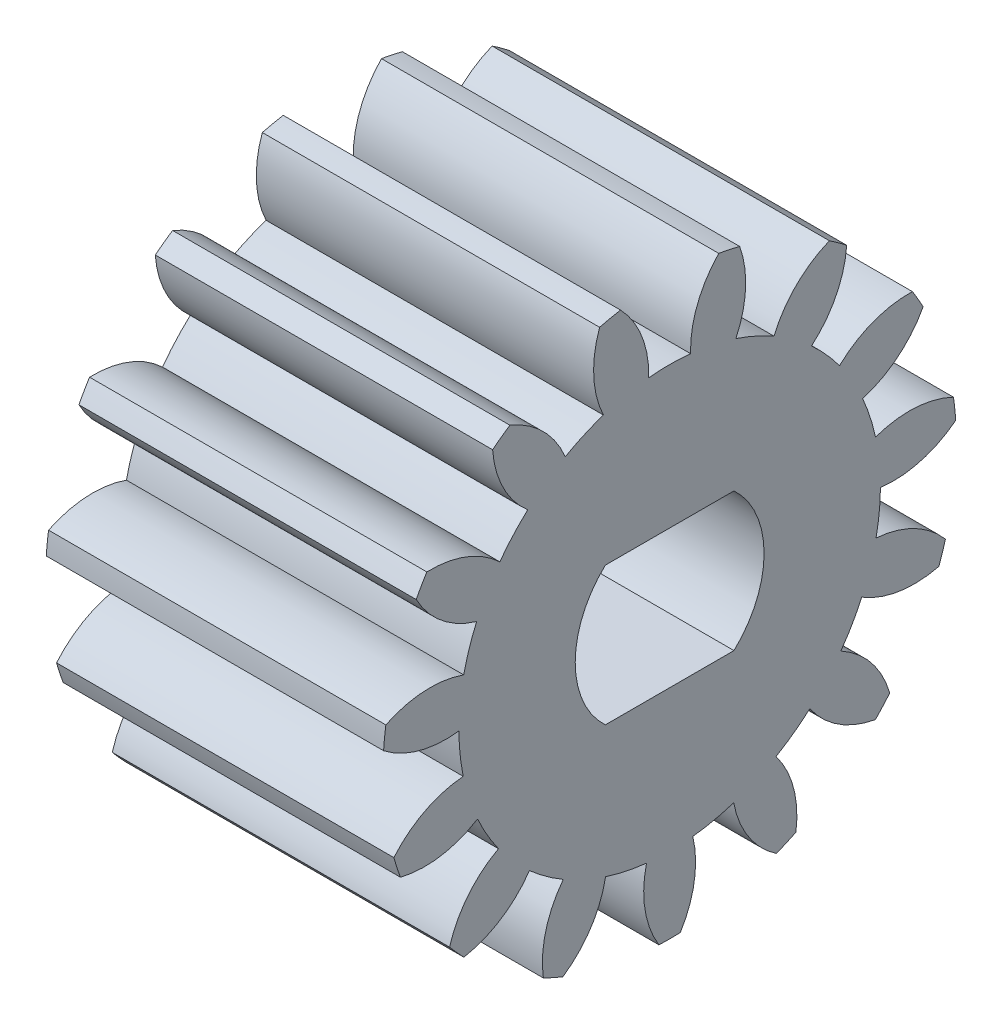
SolidWorks part; units mm, degrees
ref_plane "Plane1" through (0, 0, 0) normal (0, 0, 1) x (1, 0, 0)
ref_plane "Plane2" through (0, 0, 0) normal (0, 1, 0) x (1, 0, 0)
ref_plane "Plane3" through (0, 0, 0) normal (1, 0, 0) x (0, 0, -1)
sketch "HoldingSke" plane through (0, 0, 0) normal (0, 1, 0) x (1, 0, 0)
  line L0 (0, 0) -> (0.9659, -0.2588)
  line L1 (-15, 0) -> (100, 0) construction
  line L2 (0, 0) -> (-2.1039, 2.3779)
  line L3 (0, 0) -> (-11.863, 4.5341)
  line L4 (0, 0) -> (8.3417, 2.2352)
  line L5 (0, 0) -> (-46.8476, -17.4728)
  line L6 (0, 0) -> (-8.2896, -5.593)
  line L7 (-2.1039, 2.3779) -> (8.6586, 51.2059)
  line L8 (-76.2, 54.61) -> (-75.3, 54.61)
  line L9 (-67.7845, 28.3722) -> (-49.3413, 33.142)
  line L10 (-76.2, 71.12) -> (104.1128, 71.12)
  line L11 (0, 0) -> (-10, 0)
  line L12 (-76.2, 101.6) -> (-76.162, 101.6)
  line L13 (24.9733, 27.94) -> (52.9518, 28.4284)
  line L14 (24.9733, 27.94) -> (24.9743, 27.94)
  line L15 (24.9733, 27.94) -> (100.4006, 29.5858)
  line L16 (-63.627, -1) -> (-12.827, -1)
  circle A0 centre (0, 0) radius 2.5
  circle A1 centre (0, 0) radius 6.249
  circle A2 centre (0, 0) radius 37.5
  circle A3 centre (0, 0) radius 2.5
  dimension "MHD" = 12.498
  dimension "Hub_dia" = 75
  dimension "Bore" = 5
  dimension "MBD" = 5
  dimension "Num_teeth" = 15
  dimension "Pitch" = 1
  dimension "Overall_len" = 50
  dimension "Show_teeth" = 15
  dimension "Thickness" = 10
  dimension "OAL" = 50.0001
  dimension "T_dim" = 0.9
  dimension "Ap" = 14.5
  dimension "H" = 19.05
  dimension "Pitch_radius" = 180.3128
  dimension "Width" = 10
  dimension "Backlash" = 0.038
  dimension "Addendum_fac" = 1
  dimension "Dedendum_fac" = 1.25
  dimension "Clearance_fac" = 0.25
  dimension "Dedendum_add" = 0.001
  dimension "Module" = 1
sketch "BasProSke" plane through (0, 0, 0) normal (0, 1, 0) x (1, 0, 0)
  line L0 (-10, 0) -> (60, 0) construction
  line L1 (0, 0) -> (0, 8.5)
  line L2 (0, 0) -> (10, 0)
  line L3 (10, 0) -> (10, 8.5)
  line L4 (10, 8.5) -> (0, 8.5)
  dimension "Thickness" = 10
  dimension "Diameter" = 17
revolve "Base-Revolve" add sketch "BasProSke" angle 360 about L0
sketch "TooCutSke" plane through (0, 0, 0) normal (1, 0, 0) x (0, 0, -1)
  line L1 (0, 0) -> (0, 107) construction
  line L2 (0, 0) -> (-0.8504, 7.4516) construction
  line L3 (0, 0) -> (-3.1044, 14.6049) construction
  line L4 (-0.8504, 7.4516) -> (-1.5522, 7.3025) construction
  arc A0 (0.6195, 6.2182) -> (-0.6195, 6.2182) centre (0, 0) ccw
  arc A1 (1.4773, 8.3964) -> (-1.4773, 8.3964) centre (0, 0) ccw
  circle A2 centre (0, 0) radius 7.5 construction
  circle A3 centre (0, 0) radius 7.2611 construction
  arc A4 (-0.6195, 6.2182) -> (-1.4773, 8.3964) centre (-3.6186, 6.2952) ccw
  arc A5 (1.4773, 8.3964) -> (0.6195, 6.2182) centre (3.6186, 6.2952) ccw
  dimension "Root_dia" = 12.498
  dimension "Overcut_dia" = 17.0508
  dimension "Pitch_dia" = 15
  dimension "Base_dia" = 14.5222
  dimension "Flank_rad" = 3
  dimension "Half_ang" = 12
  dimension "Half_CT" = 0.7175
extrude "ToothCut" cut sketch "TooCutSke" along normal through all
fillet "Breaks" [suppressed] radius 0.02 tangent propagation no
fillet "RootFillets" [suppressed] radius 0.251
pattern_circular "TeethCuts" count 15 every 24 about axis through (-10, 0, 0) along (1, 0, 0) of "ToothCut", "RootFillets", "Breaks"
sketch "HubNeaOneSke" plane through (0, 0, 0) normal (-1, 0, 0) x (0, 0, 1)
  circle A0 centre (0, 0) radius 6.249
  dimension "Diameter" = 12.498
extrude "HubNearOne" [suppressed] add sketch "HubNeaOneSke" along normal blind 40.0001
sketch "HubNeaBotSke" plane through (0, 0, 0) normal (-1, 0, 0) x (0, 0, 1)
  circle A0 centre (0, 0) radius 6.249
  dimension "Diameter" = 12.498
extrude "HubNearBoth" [suppressed] add sketch "HubNeaBotSke" along normal blind 20
ref_plane "FarPln" through (10, 0, 0) normal (1, 0, 0) x (0, 0, -1)
sketch "HubFarSke" plane through (10, 0, 0) normal (1, 0, 0) x (0, 0, -1)
  circle A0 centre (0, 0) radius 6.249
  dimension "Diameter" = 12.498
extrude "HubFar" [suppressed] add sketch "HubFarSke" along normal blind 20
sketch "BorSke" plane through (0, 0, 0) normal (1, 0, 0) x (0, 0, -1)
  circle A0 centre (0, 0) radius 2.5
  dimension "Diameter" = 5
extrude "Bore" cut sketch "BorSke" along normal mid plane 100.0001
sketch "KeySke" plane through (0, 0, 0) normal (1, 0, 0) x (0, 0, -1)
  line L0 (-1, 0) -> (-1, 3.4)
  line L1 (-1, 3.4) -> (1, 3.4)
  line L2 (1, 3.4) -> (1, 0)
  line L3 (0, 0) -> (0, 34) construction
  line L4 (-1, 0) -> (1, 0)
  dimension "Offset" = 3.4
  dimension "Width" = 2
extrude "Keyway" [suppressed] cut sketch "KeySke" along normal mid plane 100.0001
pattern_circular "Keyway2" [suppressed] count 2 every 90 about axis through (-10, 0, 0) along (1, 0, 0) reverse direction yes
sketch "Sketch1" plane through (10, 0, 0) normal (1, 0, 0) x (0, 0, -1)
  line L0 (-1.9072, 2.05) -> (1.9072, 2.05)
  line L1 (-1.9072, -2.05) -> (1.9072, -2.05)
  circle A0 centre (0, 0) radius 2.8
  dimension "D1" = 5.6
  dimension "D2" = 4.1
  dimension "D3" = 2.05
extrude "Boss-Extrude1" add sketch "Sketch1" against normal through all contours L0 A0 | L1 A0 region at (10, 2.3537, 0) region at (10, -2.3537, 0)
extrude "Cut-Extrude1" cut sketch "Sketch1<3>" against normal blind 10 contours L0 A0 L1 region at (10, 0, 0)
sketch "Sketch1<3>" plane through (10, 0, 0) normal (1, 0, 0) x (0, 0, -1) same geometry as "Sketch1"
equation "' \"Module@HoldingSke\" = 6.35"
equation "' \"Num_teeth@HoldingSke\" = 12"
equation "' \"Ap@HoldingSke\" =  20"
equation "' \"Ap@HoldingSke\" = 20"
equation "' \"Width@HoldingSke\" = 0.5 * 25.4"
equation "' \"Hub_dia@HoldingSke\"= 1 * 25.4"
equation "' \"Hub_dia@HoldingSke\" = 1 * 25.4"
equation "' \"Overall_len@HoldingSke\" = 1.0 * 25.4"
equation "' \"Bore@HoldingSke\" = 0.75 * 25.4"
equation "' \"T_dim@HoldingSke\" = 0.1 * 25.4"
equation "' \"Width@KeySke\" = 0.25 * 25.4"
equation "' \"Show_teeth@HoldingSke\" = 13"
equation "' \"Backlash@HoldingSke\" = 0.009 * 25.4"
equation "' \"Addendum_fac@HoldingSke\" = 1.0"
equation "' \"Dedendum_fac@HoldingSke\" = 1.25"
equation "' \"Dedendum_add@HoldingSke\" = 0.00005 * 25.4"
equation "' \"Clearance_fac@HoldingSke\" = 0.25"
equation "\"Pitch@HoldingSke\" = 1 / \"Module@HoldingSke\""
equation "\"Overcut_dia@TooCutSke\" = (\"Num_teeth@HoldingSke\" + 2 * \"Addendum_fac@HoldingSke\") / \"Pitch@HoldingSke\" + 0.002 * 25.4"
equation "\"Pitch_dia@TooCutSke\" = \"Num_teeth@HoldingSke\" / \"Pitch@HoldingSke\""
equation "\"Base_dia@TooCutSke\" = \"Num_teeth@HoldingSke\" / \"Pitch@HoldingSke\" * cos((\"Ap@HoldingSke\"  * 3.14159265 / 180))"
equation "\"Root_dia@TooCutSke\" = (\"Num_teeth@HoldingSke\" + 2) / \"Pitch@HoldingSke\" - 2 * (\"Addendum_fac@HoldingSke\" + \"Dedendum_fac@HoldingSke\") / \"Pitch@HoldingSke\" - \"Dedendum_add@HoldingSke\" * 2"
equation "\"Half_ang@TooCutSke\" = 180 / \"Num_teeth@HoldingSke\""
equation "\"Half_CT@TooCutSke\" = \"Num_teeth@HoldingSke\" / \"Pitch@HoldingSke\" * sin((3.14159265 / 2 / \"Num_teeth@HoldingSke\")) / 2 - 7 * \"Backlash@HoldingSke\" / 4"
equation "\"Flank_rad@TooCutSke\" = \"Num_teeth@HoldingSke\" / \"Pitch@HoldingSke\" / 5"
equation "\"Radius@RootFillets\" = \"Clearance_fac@HoldingSke\" / \"Pitch@HoldingSke\" + \"Dedendum_add@HoldingSke\""
equation "\"Break_rad@Breaks\" = 0.02 / \"Pitch@HoldingSke\""
equation "\"Thickness@HoldingSke\" = \"Width@HoldingSke\""
equation "\"OAL@HoldingSke\" = \"Thickness@HoldingSke\""
equation "\"MHD@HoldingSke\" = (\"Num_teeth@HoldingSke\" + 2) / \"Pitch@HoldingSke\" - 2 * (\"Addendum_fac@HoldingSke\" + \"Dedendum_fac@HoldingSke\")  / \"Pitch@HoldingSke\" - \"Dedendum_add@HoldingSke\" * 2"
equation "\"MBD@HoldingSke\" = (\"Num_teeth@HoldingSke\" + 2) / \"Pitch@HoldingSke\" - 2 * (\"Addendum_fac@HoldingSke\" + \"Dedendum_fac@HoldingSke\")  / \"Pitch@HoldingSke\" - \"Dedendum_add@HoldingSke\" * 2 - 0.002 * 25.4"
equation "\"MHD@HoldingSke\" = ((sgn( \"MHD@HoldingSke\" - \"Hub_dia@HoldingSke\" )-1)*( \"MHD@HoldingSke\" - \"Hub_dia@HoldingSke\" ))/-2+ \"Hub_dia@HoldingSke\""
equation "\"MBD@HoldingSke\" = ((sgn( \"MBD@HoldingSke\" - \"Bore@HoldingSke\" )-1)*( \"MBD@HoldingSke\" - \"Bore@HoldingSke\" ))/-2+ \"Bore@HoldingSke\""
equation "\"OAL@HoldingSke\" = ((sgn( \"OAL@HoldingSke\" - \"Overall_len@HoldingSke\" )+1)*( \"OAL@HoldingSke\" - \"Overall_len@HoldingSke\" ))/2 + \"Overall_len@HoldingSke\" + 0.000002 * 25.4"
equation "\"Num_teeth@TeethCuts\" = int( \"Show_teeth@HoldingSke\" ) + 1"
equation "\"Num_teeth@TeethCuts\" = ((sgn( \"Num_teeth@TeethCuts\" - \"Num_teeth@HoldingSke\" )-1)*( \"Num_teeth@TeethCuts\" - \"Num_teeth@HoldingSke\" ))/-2+ \"Num_teeth@HoldingSke\""
equation "\"Num_teeth@TeethCuts\" = ((sgn( \"Num_teeth@TeethCuts\" - 2.0)+1)*( \"Num_teeth@TeethCuts\" - 2.0))/2 +2.0"
equation "\"Angle@TeethCuts\" = 360.0 / \"Num_teeth@HoldingSke\""
equation "\"Diameter@BasProSke\" = (\"Num_teeth@HoldingSke\" + 2 * \"Addendum_fac@HoldingSke\") / \"Pitch@HoldingSke\""
equation "\"Thickness@BasProSke\"  = \"Thickness@HoldingSke\""
equation "' \"Fillet_rad@BasProSke\" =  \"Thickness@HoldingSke\" * 0.05"
equation "' \"Fillet_rad@BasProSke\" = \"Thickness@HoldingSke\" * 0.05"
equation "\"MHD@HoldingSke\" = ((sgn( \"MHD@HoldingSke\" - \"Root_dia@TooCutSke\" )-1)*( \"MHD@HoldingSke\" - \"Root_dia@TooCutSke\" ))/-2+ \"Root_dia@TooCutSke\""
equation "\"Diameter@HubNeaOneSke\" = \"MHD@HoldingSke\""
equation "\"Length@HubNearOne\" = \"OAL@HoldingSke\" - \"Thickness@BasProSke\""
equation "\"Diameter@HubNeaBotSke\" = \"MHD@HoldingSke\""
equation "\"Length@HubNearBoth\" = ( \"OAL@HoldingSke\" - \"Thickness@BasProSke\" ) / 2.0"
equation "\"Thickness@FarPln\" = \"Thickness@BasProSke\""
equation "\"Diameter@HubFarSke\" = \"MHD@HoldingSke\""
equation "\"Length@HubFar\" = ( \"OAL@HoldingSke\" - \"Thickness@BasProSke\" ) / 2.0"
equation "\"Diameter@BorSke\" = \"MBD@HoldingSke\""
equation "\"D1@Bore\" = \"OAL@HoldingSke\" * 2.0"
equation "\"D1@Keyway\" = \"OAL@HoldingSke\" * 2.0"
equation "\"Offset@KeySke\" = \"T_dim@HoldingSke\" + \"MBD@HoldingSke\" / 2.0"
equation "\"D3@Sketch1\"=\"D2@Sketch1\"/2"
